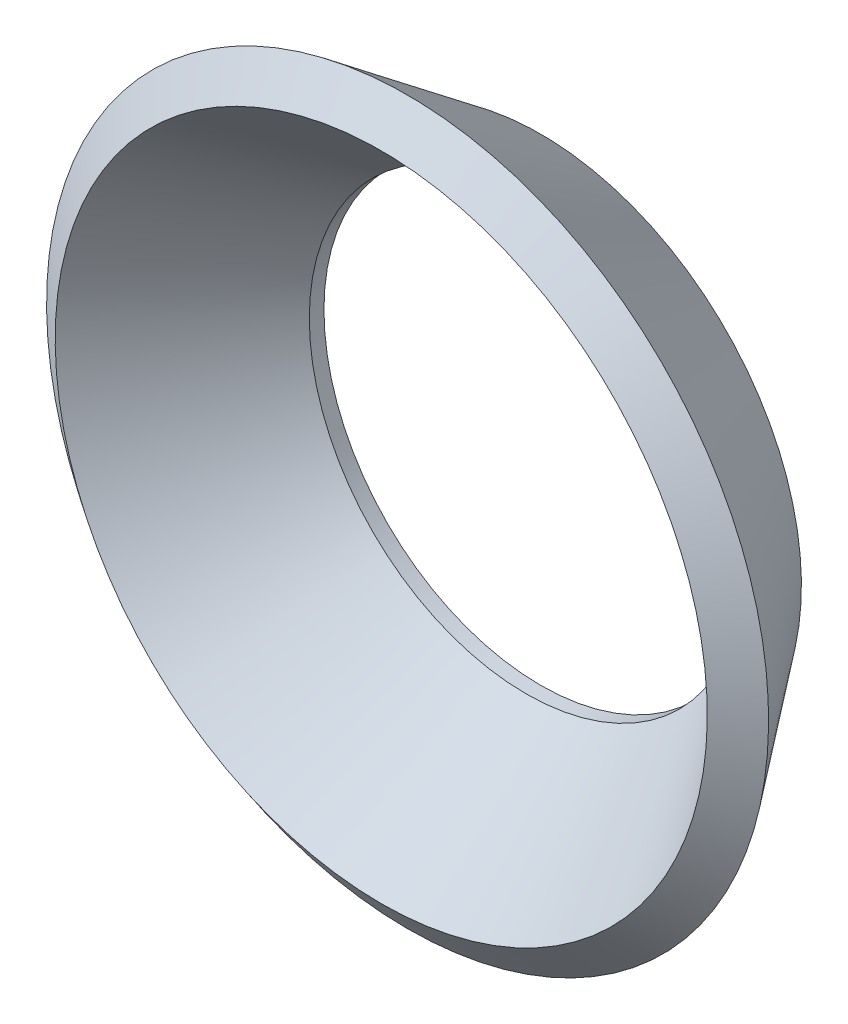
SolidWorks part; units mm, degrees
ref_plane "Front Plane" through (0, 0, 0) normal (0, 0, 1) x (1, 0, 0)
ref_plane "Top Plane" through (0, 0, 0) normal (0, 1, 0) x (1, 0, 0)
ref_plane "Right Plane" through (0, 0, 0) normal (1, 0, 0) x (0, 0, -1)
sketch "Sketch2" plane through (0, 0, 0) normal (1, 0, 0) x (0, 0, -1)
  line L0 (0, 5.2832) -> (0, 0) construction
  line L7 (0, 0) -> (17.2695, 0) construction
  line L14 (0, 5.2832) -> (-3.1735, 5.2832) construction
  line L27 (0, 6.35) -> (-3.2457, 8.7958)
  line L31 (0, 5.2832) -> (0, 6.35)
  line L32 (-0.642, 5.498) -> (-3.8877, 7.9438)
  line L33 (-0.642, 5.498) -> (-0.3569, 5.2832)
  line L34 (-0.3569, 5.2832) -> (0, 5.2832)
  line L35 (-3.2457, 8.7958) -> (-3.8877, 7.9438)
  line L36 (55, 0) -> (-55, 0) construction
  dimension "D1" = 1.0668
  dimension "D6" = 37
  dimension "D2" = 1.0668
  dimension "D3" = 6.35
  dimension "D4" = 4.064
revolve "Revolve1" add sketch "Sketch2" angle 360 about L7
sketch "Sketch3" plane through (0, 0, 0) normal (0, 0, 1) x (1, 0, 0)
  point P0 (0, 0)
